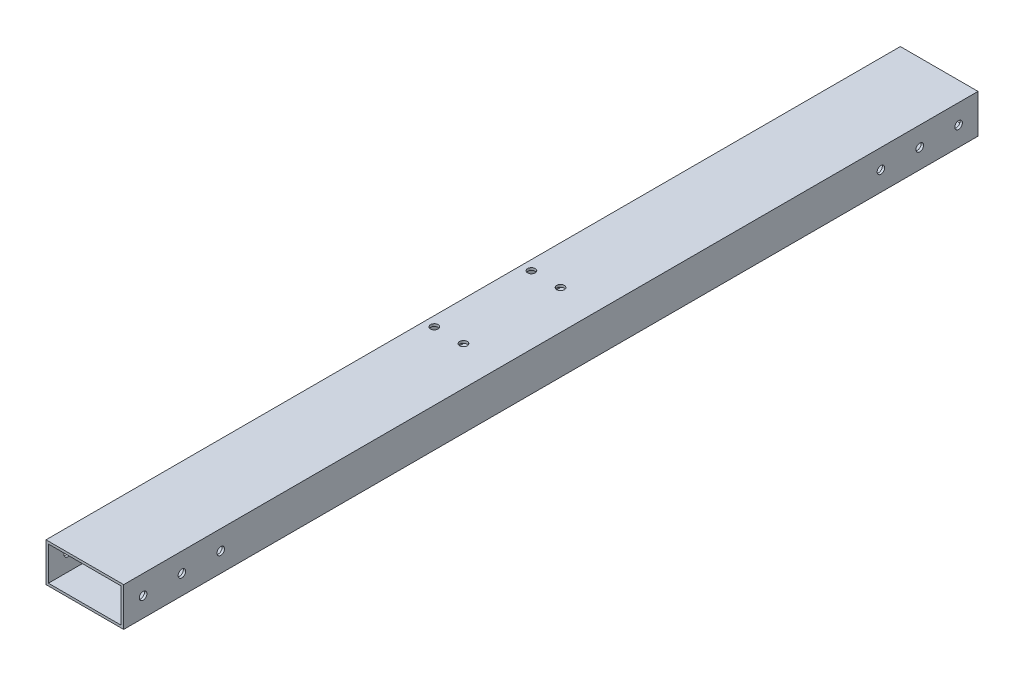
SolidWorks part; units mm, degrees
material "6061-T6 (SS)"
ref_plane "Front Plane" through (0, 0, 0) normal (0, 0, 1) x (1, 0, 0)
ref_plane "Top Plane" through (0, 0, 0) normal (0, 1, 0) x (1, 0, 0)
ref_plane "Right Plane" through (0, 0, 0) normal (1, 0, 0) x (0, 0, -1)
sketch "Sketch1" plane through (0, 0, 0) normal (0, 0, 1) x (1, 0, 0)
  line L1 (-25.4, -12.7) -> (25.4, -12.7)
  line L2 (-25.4, -12.7) -> (-25.4, 12.7)
  line L3 (-25.4, 12.7) -> (25.4, 12.7)
  line L4 (25.4, -12.7) -> (25.4, 12.7)
  line L5 (-25.4, -12.7) -> (25.4, 12.7) construction
  line L6 (-25.4, 12.7) -> (25.4, -12.7) construction
  point P0 (0, 0)
  dimension "D1" = 50.8
  dimension "D2" = 25.4
extrude "Boss-Extrude1" add sketch "Sketch1" along normal mid plane 558.8
shell "Shell1" thickness 1.5875 removed face at (0, 0, -279.4) removed face at (0, 0, 279.4)
sketch "Sketch3" plane through (0, 0, 0) normal (1, 0, 0) x (0, 0, -1)
  line L0 (-279.4, -12.7) -> (-279.4, 12.7) construction
  line L1 (0, 12.7) -> (0, -12.7) construction
  line L2 (-279.4, 12.7) -> (279.4, 12.7) construction
  line L3 (-279.4, -12.7) -> (279.4, -12.7) construction
  circle A0 centre (-266.7, 0) radius 2.4892
  circle A1 centre (-241.3, 0) radius 2.4892
  circle A2 centre (-215.9, 0) radius 2.4892
  circle A3 centre (215.9, 0) radius 2.4892
  circle A4 centre (241.3, 0) radius 2.4892
  circle A5 centre (266.7, 0) radius 2.4892
  dimension "D2" = 4.9784
  dimension "D1" = 12.7
  dimension "D3" = 25.4
  dimension "D4" = 25.4
  dimension "D5" = 12.7
extrude "Cut-Extrude1" cut sketch "Sketch3" against normal through all both and the other way through all
sketch "Sketch4" plane through (0, 0, 0) normal (0, 1, 0) x (1, 0, 0)
  line L1 (-25.4, -279.4) -> (-25.4, 279.4) construction
  circle A0 centre (0, -31.75) radius 2.4892
  circle A1 centre (-19.05, -31.75) radius 2.4892
  circle A2 centre (0, 31.75) radius 2.4892
  circle A3 centre (-19.05, 31.75) radius 2.4892
  dimension "D1" = 4.9784
  dimension "D3" = 19.05
  dimension "D4" = 31.75
  dimension "D2" = 6.35
  dimension "D5" = 63.5
extrude "Cut-Extrude2" cut sketch "Sketch4" against normal through all both and the other way through all
equation "\"D4@Sketch3\"=\"D3@Sketch3\""
equation "\"D4@Sketch4\"=1.5-.25"
